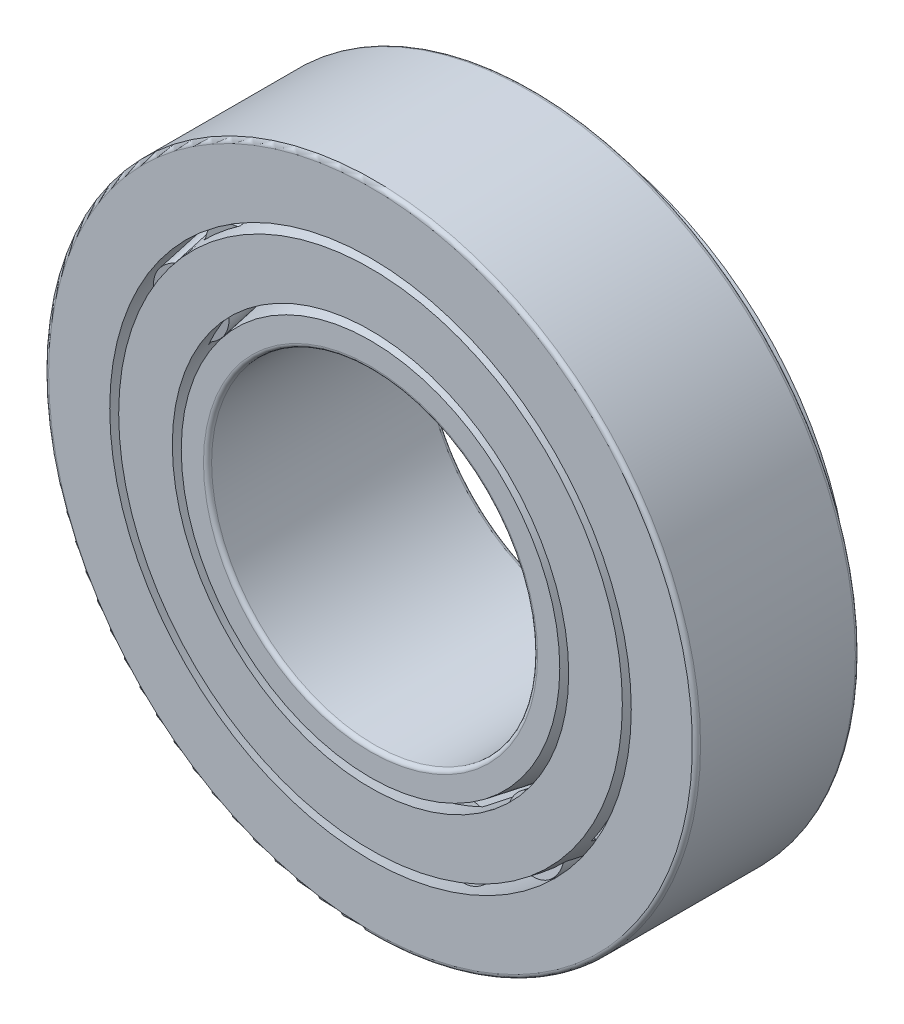
SolidWorks part; units mm, degrees
material "Plain Carbon Steel"
ref_plane "Front Plane" through (0, 0, 0) normal (0, 0, 1) x (1, 0, 0)
ref_plane "Top Plane" through (0, 0, 0) normal (0, 1, 0) x (1, 0, 0)
ref_plane "Right Plane" through (0, 0, 0) normal (1, 0, 0) x (0, 0, -1)
sketch "Sketch1" plane through (0, 0, 0) normal (1, 0, 0) x (0, 0, -1)
  line L0 (-12.8984, 0) -> (12.8984, 0) construction
  line L1 (0, 0) -> (0, 38.1) construction
  line L2 (-12.8984, 19.05) -> (12.8984, 19.05) construction
  line L3 (12.8984, 19.05) -> (12.8984, 26.67) construction
  line L4 (12.8984, 26.67) -> (-12.8984, 22.1213) construction
  line L5 (-12.8984, 22.1213) -> (-12.8984, 19.05) construction
  line L7 (-12.8984, 38.1) -> (6.1516, 38.1)
  line L8 (6.1516, 38.1) -> (6.1516, 33.839)
  line L9 (6.1516, 33.839) -> (-12.8984, 30.48)
  line L10 (-12.8984, 30.48) -> (-12.8984, 38.1)
  line L11 (-12.8984, 30.48) -> (-11.469, 22.3734) construction
  line L12 (9.4846, 34.4267) -> (10.9141, 26.3201) construction
  line L14 (-12.8984, 22.1213) -> (-11.469, 22.3734) construction
  line L15 (-12.8984, 22.1213) -> (10.9141, 26.3201) construction
  point P5 (0, 19.05)
  dimension "D1" = 100
  dimension "Width" = 25.7969
  dimension "OD" = 76.2
  dimension "Shaft Dia" = 38.1
  dimension "D2" = 19.05
  dimension "D3" = 7.62
  dimension "Outer Wd" = 19.05
  dimension "Bearing Wd" = 23.8125
revolve "Revolve1" add sketch "Sketch1" angle 360 about L0
sketch "Sketch5" plane through (0, 0, 0) normal (1, 0, 0) x (0, 0, -1)
  line L0 (12.8984, 26.67) -> (-12.8984, 22.1213) construction
  line L1 (12.8984, 26.67) -> (-12.8984, 22.1213)
  line L2 (-12.8984, 22.1213) -> (-12.8984, 19.05)
  line L3 (-12.8984, 19.05) -> (12.8984, 19.05)
  line L4 (12.8984, 19.05) -> (12.8984, 26.67)
revolve "Revolve4" add sketch "Sketch5" angle 360 about L0
sketch "Sketch2" plane through (0, 0, 0) normal (1, 0, 0) x (0, 0, -1)
  line L0 (-12.8984, 29.4352) -> (-12.8984, 23.1662)
  line L1 (6.1516, 32.7942) -> (9.6633, 33.4134)
  line L2 (-12.8984, 23.1662) -> (6.1516, 26.5252)
  line L3 (9.4846, 34.4267) -> (10.9141, 26.3201) construction
  line L4 (6.1516, 26.5252) -> (6.1516, 32.7942) construction
  line L5 (6.1516, 32.7942) -> (-12.8984, 29.4352)
  line L6 (6.1516, 33.839) -> (-12.8984, 30.48) construction
  line L7 (12.8984, 26.67) -> (-12.8984, 22.1213) construction
  line L8 (-12.8984, 30.48) -> (6.1516, 33.839) construction
  line L9 (-12.8984, 22.1213) -> (10.9141, 26.3201) construction
  line L10 (9.6633, 33.4134) -> (10.7354, 27.3334)
  line L11 (-12.8984, 30.48) -> (-12.8984, 29.4352) construction
  line L12 (-12.8984, 23.1662) -> (-12.8984, 22.1213) construction
  line L13 (6.1516, 38.1) -> (6.1516, 33.839) construction
  line L14 (10.7354, 27.3334) -> (6.1516, 26.5252)
  dimension "D1" = 8.2317
  dimension "D2" = 6.1738
revolve "Revolve2" add sketch "Sketch2" angle 360 about L0
sketch "Sketch3" plane through (0, 0, 0) normal (1, 0, 0) x (0, 0, -1)
  line L0 (-12.8984, 26.3007) -> (6.1516, 29.6597) construction
  line L1 (-12.8984, 29.4352) -> (-12.8984, 23.1662) construction
  line L2 (6.1516, 26.5252) -> (6.1516, 32.7942) construction
  line L3 (-10.7543, 26.6787) -> (-11.469, 30.732)
  line L5 (-11.469, 30.732) -> (5.4369, 33.713)
  line L6 (5.4369, 33.713) -> (6.1516, 29.6597)
  line L7 (6.1516, 29.6597) -> (-10.7543, 26.6787)
  line L8 (6.1516, 33.839) -> (-12.8984, 30.48) construction
  line L9 (-12.8984, 26.3007) -> (-12.1837, 26.4267) construction
  line L10 (-12.8984, 30.48) -> (-11.469, 22.3734) construction
  line L11 (-12.1837, 26.4267) -> (-11.469, 26.5527) construction
  line L12 (-11.469, 26.5527) -> (-10.7543, 26.6787) construction
revolve "Cut-Revolve1" cut sketch "Sketch3" angle 360 about L0
sketch "Sketch4" plane through (0, 0, 0) normal (1, 0, 0) x (0, 0, -1)
  line L0 (-11.4249, 30.4819) -> (5.481, 33.4629)
  line L1 (5.481, 33.4629) -> (6.1516, 29.6597)
  line L2 (6.1516, 29.6597) -> (-10.7543, 26.6787)
  line L3 (-12.8984, 26.3007) -> (-10.7543, 26.6787) construction
  line L4 (-10.7543, 26.6787) -> (-11.4249, 30.4819)
  line L6 (6.1516, 29.6597) -> (-10.7543, 26.6787) construction
  line L7 (6.1516, 33.839) -> (-12.8984, 30.48) construction
  dimension "D1" = 0.254
revolve "Revolve3" add sketch "Sketch4" angle 360 about L0
ref_axis "Axis1" through (0, 0, -12.8984) along (0, 0, 1)
pattern_circular "CirPattern1" count 18 over 360 about axis through (0, 0, -12.8984) along (0, 0, 1) of "Cut-Revolve1"
pattern_circular "CirPattern2" count 18 over 360 about axis through (0, 0, -12.8984) along (0, 0, 1) of bodies 403
fillet "Fillet1" radius 0.4763 2 edges at (38.1, 0, -6.1516) (38.1, 0, 12.8984)
fillet "Fillet2" radius 0.4763 2 edges at (19.05, 0, -12.8984) (19.05, 0, 12.8984)
sketch "Sketch6" plane through (0, 0, 0) normal (1, 0, 0) x (0, 0, -1)
  line L0 (-70.0484, 38.1) -> (-70.0484, 30.48)
  line L1 (-70.0484, 30.48) -> (-50.9984, 33.839)
  line L2 (-50.9984, 33.839) -> (-50.9984, 38.1)
  line L3 (-50.9984, 38.1) -> (-70.0484, 38.1)
  line L4 (-12.8984, 38.1) -> (6.1516, 38.1) construction
  line L5 (-12.8984, 30.48) -> (-12.8984, 38.1) construction
  line L6 (6.1516, 38.1) -> (6.1516, 33.839) construction
  dimension "Ring Separation" = 38.1
revolve "Revolve5" [suppressed] add sketch "Sketch6" angle 360 about L0
fillet "Fillet3" [suppressed] radius 0.4763
delete or keep bodies "Body-Delete1" [suppressed] type delete bodies bodies 399
sketch "Sketch8" plane through (0, 0, 0) normal (0, 0, 1) x (1, 0, 0)
  line L0 (0, 47.625) -> (0, -47.625) construction
  dimension "D1" = 95.25
equation "\"D3@Sketch1\" = \"D2@Sketch1\"/2.5"
equation "\"D2@Sketch2\" = \"D1@Sketch2\"*.75"
equation "\"D1@Fillet1\" = \"Outer Wd@Sketch1\"*.025"
equation "\"D1@Fillet2\" = \"D1@Fillet1\""
equation "\"D1@Fillet3\" = \"D1@Fillet1\""
equation "\"Rollers@CirPattern2\" = \"D1@CirPattern1\""
equation "\"D1@Sketch8\" = \"OD@Sketch1\"*1.250"
